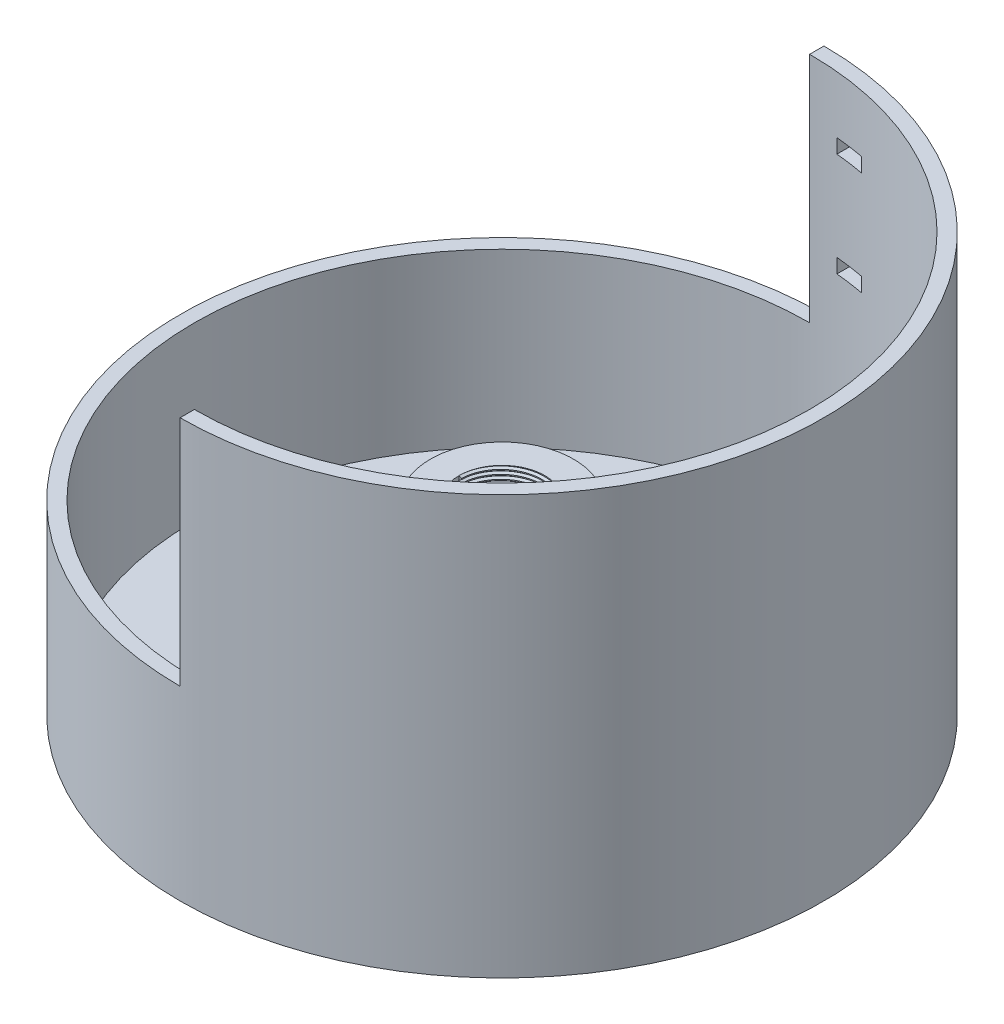
SolidWorks part; units mm, degrees
ref_plane "Front Plane" through (0, 0, 0) normal (0, 0, 1) x (1, 0, 0)
ref_plane "Top Plane" through (0, 0, 0) normal (0, 1, 0) x (1, 0, 0)
ref_plane "Right Plane" through (0, 0, 0) normal (1, 0, 0) x (0, 0, -1)
sketch "Sketch1" plane through (0, 0, 0) normal (0, 1, 0) x (1, 0, 0)
  circle A0 centre (0, 0) radius 112.5
  dimension "D1" = 225
extrude "Boss-Extrude1" add sketch "Sketch1" along normal blind 65
shell "Shell1" thickness 5 removed face at (0, 65, 112.5)
sketch "Sketch2" plane through (0, 5, 0) normal (0, 1, 0) x (1, 0, 0)
  circle A0 centre (0, 0) radius 25
  dimension "D1" = 50
extrude "Boss-Extrude2" add sketch "Sketch2" along normal up to surface (60 mm away) up to face at (0, 65, 107.5)
shell "Shell2" thickness 10 removed face at (0, 65, 25)
sketch "Sketch3" plane through (0, 0, 0) normal (0, 0, 1) x (1, 0, 0)
  line L0 (0, 0) -> (0, 65) construction
  line L1 (112.5, 65) -> (-112.5, 65) construction
  circle A0 centre (0, 32.5) radius 1.25
  dimension "D1" = 2.5
extrude "Cut-Extrude1" cut sketch "Sketch3" against normal through all
sketch "Sketch6" plane through (0, 65, 0) normal (0, 1, 0) x (1, 0, 0)
  circle A0 centre (0, 0) radius 107.5
  circle A1 centre (0, 0) radius 112.5
extrude "Boss-Extrude3" add sketch "Sketch6" along normal blind 81.25
sketch "Sketch7" plane through (0, 0, 0) normal (1, 0, 0) x (0, 0, -1)
  line L0 (25, 65) -> (112.5, 65) construction
  line L1 (112.5, 33.75) -> (112.5, 146.25) construction
  line L2 (112.5, 146.25) -> (-112.5, 146.25) construction
  line L3 (112.5, 65) -> (-112.5, 65)
  line L4 (112.5, 65) -> (112.5, 146.25)
  line L5 (112.5, 146.25) -> (-112.5, 146.25)
  line L6 (-112.5, 65) -> (-112.5, 146.25)
extrude "Cut-Extrude2" cut sketch "Sketch7" against normal through all
thread "Thread1" pitch 1.5 method extrude profile "Thread Profile1" start angle 0, offset 0, length 7.5, pitch 1.5, diameter 30
ref_plane "Plane1" through (-15, 65, 0) normal (0, 0, 1) x (-1, 0, 0)
sketch "Thread Profile1" plane through (-15, 65, 0) normal (0, 0, 1) x (-1, 0, 0)
  line L0 (0, 0) -> (0, 1.5) construction
  line L11 (0, 0) -> (0, 1.3125)
  line L12 (0, 1.3125) -> (-0.8119, 0.8437)
  line L13 (-0.8119, 0.8437) -> (-0.8119, 0.4687)
  line L15 (-0.8119, 0.4687) -> (0, 0)
  line L17 (-0.8119, 0.6562) -> (0, 0.6562) construction
  point P2 (0, 0)
  dimension "Pitch" = 1.5
  dimension "Profile_Angle" = 60
  dimension "Profile_Land" = 0.375
  dimension "Profile_Height" = 0.8119
sketch "Sketch15" plane through (0, 0, 0) normal (0, 0, 1) x (1, 0, 0)
  line L0 (0, 65) -> (-112.5, 65) construction
  line L1 (10, 85) -> (20, 85)
  line L2 (10, 85) -> (10, 90)
  line L3 (10, 90) -> (20, 90)
  line L4 (20, 85) -> (20, 90)
  line L5 (10, 121.25) -> (20, 121.25)
  line L6 (10, 121.25) -> (10, 126.25)
  line L7 (10, 126.25) -> (20, 126.25)
  line L8 (20, 121.25) -> (20, 126.25)
  line L9 (112.5, 146.25) -> (0, 146.25) construction
  line L10 (0, 65) -> (0, 146.25) construction
  dimension "D1" = 10
  dimension "D2" = 10
  dimension "D3" = 5
  dimension "D4" = 5
  dimension "D5" = 20
  dimension "D6" = 20
  dimension "D7" = 10
  dimension "D8" = 10
extrude "Cut-Extrude3" cut sketch "Sketch15" against normal through all
